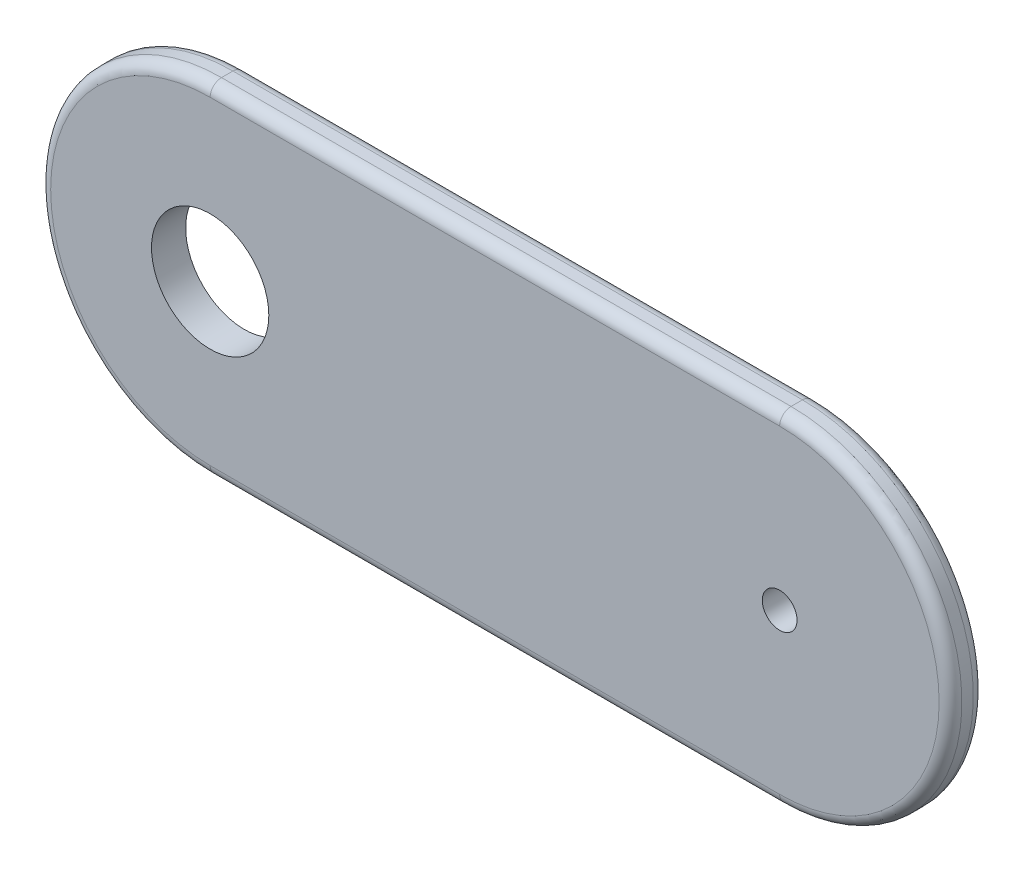
SolidWorks part; units mm, degrees
ref_plane "前视基准面" through (0, 0, 0) normal (0, 0, 1) x (1, 0, 0)
ref_plane "上视基准面" through (0, 0, 0) normal (0, 1, 0) x (1, 0, 0)
ref_plane "右视基准面" through (0, 0, 0) normal (1, 0, 0) x (0, 0, -1)
sketch "草图1" plane through (0, 0, 0) normal (0, 0, 1) x (1, 0, 0)
  line L0 (0, 0) -> (50, 0) construction
  line L1 (0, 15) -> (50, 15)
  line L2 (0, -15) -> (50, -15)
  arc A0 (0, 15) -> (0, -15) centre (0, 0) ccw
  arc A1 (50, -15) -> (50, 15) centre (50, 0) ccw
  circle A2 centre (50, 0) radius 1.525
  point P3 (25, 0)
  dimension "D2" = 15
  dimension "D3" = 3.05
  dimension "D1" = 50
extrude "凸台-拉伸1" add sketch "草图1" along normal blind 3 contours L1 A1 L2 A0
sketch "草图2" plane through (0, 0, 3) normal (0, 0, 1) x (1, 0, 0)
  circle A2 centre (0, 0) radius 5.15
  dimension "D1" = 10.3
extrude "切除-拉伸1" cut sketch "草图1<3>" along normal blind 5 contours A2 region at (50, 0, 0)
sketch "草图1<3>" plane through (0, 0, 0) normal (0, 0, 1) x (1, 0, 0) same geometry as "草图1"
fillet "圆角1" radius 1 8 edges at (-15, 0, 0) (25, -15, 0) (65, 0, 0) (-15, 0, 3) (25, -15, 3) (65, 0, 3) (25, 15, 0) (25, 15, 3)
extrude "切除-拉伸2" cut sketch "草图2" against normal blind 5
